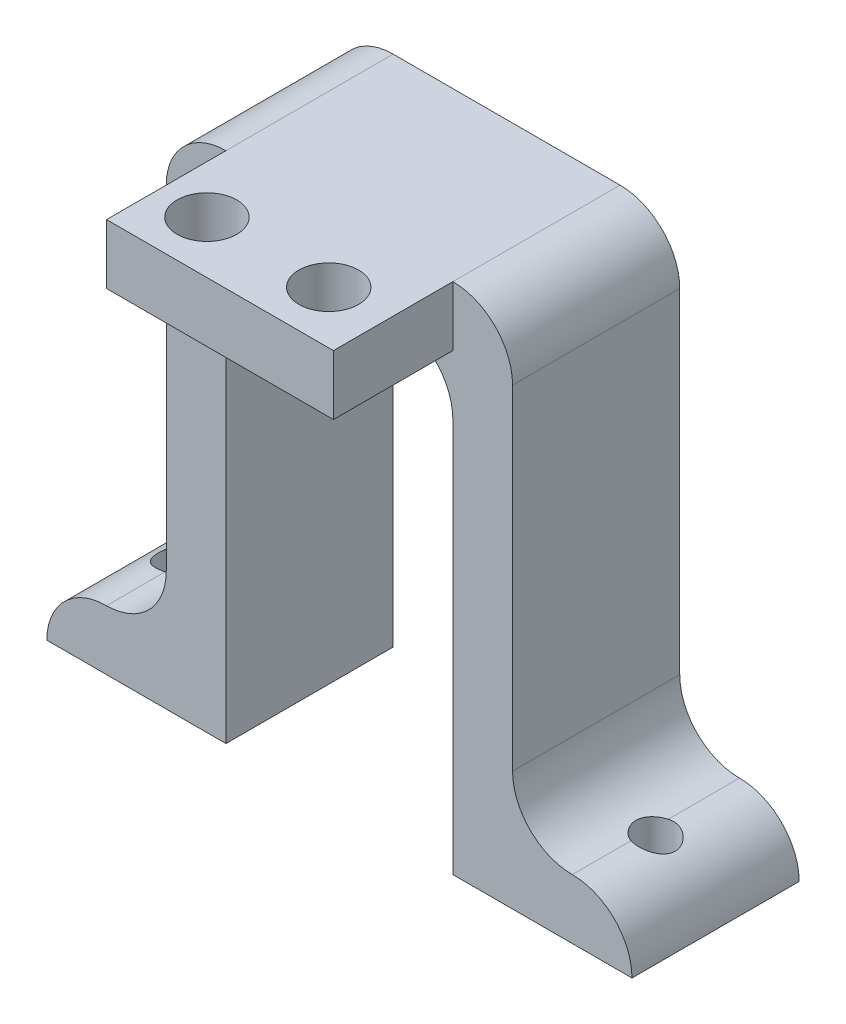
SolidWorks part; units mm, degrees
ref_plane "Front Plane" through (0, 0, 0) normal (0, 0, 1) x (1, 0, 0)
ref_plane "Top Plane" through (0, 0, 0) normal (0, 1, 0) x (1, 0, 0)
ref_plane "Right Plane" through (0, 0, 0) normal (1, 0, 0) x (0, 0, -1)
sketch "Sketch1" plane through (0, 0, 0) normal (0, 0, 1) x (1, 0, 0)
  line L0 (-24.5, 0) -> (-24.5, 5)
  line L1 (7.7, 0) -> (-7.7, 0) construction
  line L2 (-24.5, 5) -> (-14.5, 5)
  line L3 (-14.5, 5) -> (-14.5, 43)
  line L4 (-14.5, 43) -> (14.5, 43)
  line L5 (-24.5, 0) -> (-9.5, 0)
  line L6 (-9.5, 0) -> (-9.5, 38)
  line L7 (-9.5, 38) -> (9.5, 38)
  line L8 (0, -16.5) -> (0, 16.5) construction
  line L9 (24.5, 0) -> (9.5, 0)
  line L10 (24.5, 0) -> (24.5, 5)
  line L11 (24.5, 5) -> (14.5, 5)
  line L12 (9.5, 0) -> (9.5, 38)
  line L13 (14.5, 5) -> (14.5, 43)
  point P7 (0, 38)
  point P19 (0, 43)
  dimension "D1" = 19
  dimension "D2" = 5
  dimension "D3" = 5
  dimension "D4" = 5
  dimension "D5" = 10
  dimension "D6" = 38
extrude "Boss-Extrude1" add sketch "Sketch1" along normal blind 14
fillet "Fillet1" radius 5 6 edges at (-14.5, 43, 7) (14.5, 43, 7) (24.5, 5, 7) (-24.5, 5, 7) (14.5, 5, 7) (-14.5, 5, 7)
fillet "Fillet2" radius 5 2 edges at (9.5, 38, 7) (-9.5, 38, 7)
sketch "Sketch2" plane through (0, 0, 0) normal (0, 1, 0) x (1, 0, 0)
  line L0 (0, -16.5) -> (0, 16.5) construction
  circle A0 centre (-20, -7.5233) radius 1.636
  circle A1 centre (20, -7.5233) radius 1.636
  point P6 (-26.6379, -3.9367)
  point P7 (-20, -7.5233)
  point P8 (0, 0)
  point P9 (0, 0)
  dimension "D1" = 40
extrude "Cut-Extrude3" cut sketch "Sketch2" against normal blind 10 and the other way blind 10 contours A0 | A1
sketch "Sketch4" plane through (0, 0, 14) normal (0, 0, 1) x (1, 0, 0)
  line L1 (9.5, 43) -> (-9.5, 43)
  line L2 (9.5, 43) -> (9.5, 38)
  line L3 (9.5, 38) -> (-9.5, 38)
  line L4 (-9.5, 43) -> (-9.5, 38)
extrude "Boss-Extrude2" add sketch "Sketch4" along normal blind 10
sketch "Sketch5" plane through (0, 43, 0) normal (0, 1, 0) x (1, 0, 0)
  circle A0 centre (4.7058, -19.6015) radius 2.5
  circle A1 centre (-5.4774, -19.6181) radius 2.5
  dimension "D1" = 5
  dimension "D2" = 5
extrude "Cut-Extrude4" cut sketch "Sketch5" against normal blind 10
